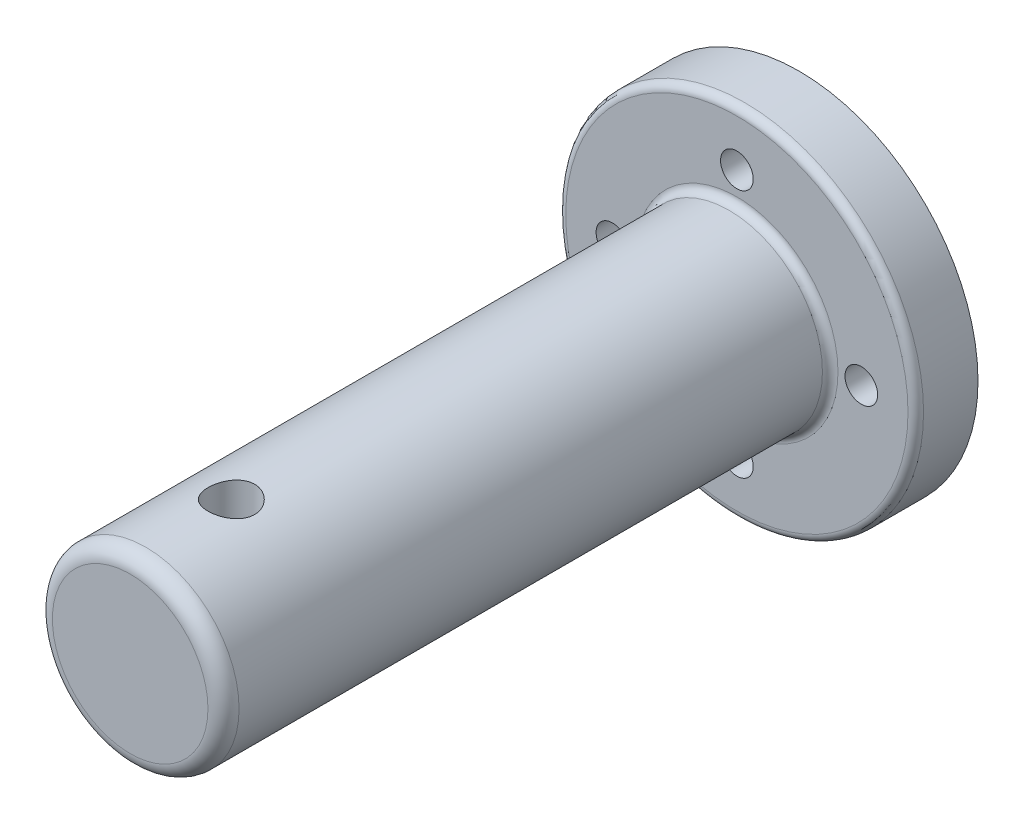
SolidWorks part; units mm, degrees
material "Alumina"
ref_plane "Front Plane" through (0, 0, 0) normal (0, 0, 1) x (1, 0, 0)
ref_plane "Top Plane" through (0, 0, 0) normal (0, 1, 0) x (1, 0, 0)
ref_plane "Right Plane" through (0, 0, 0) normal (1, 0, 0) x (0, 0, -1)
sketch "Sketch1" plane through (0, 0, 0) normal (0, 0, 1) x (1, 0, 0)
  circle A0 centre (0, 0) radius 11.5
  circle A1 centre (0, 0) radius 8 construction
  circle A2 centre (0, 8) radius 1.05
  circle A3 centre (0, 0) radius 11.5
  circle A4 centre (8, 0) radius 1.05
  circle A5 centre (0, 0) radius 11.5
  circle A6 centre (0, -8) radius 1.05
  circle A7 centre (0, 0) radius 11.5
  circle A8 centre (-8, 0) radius 1.05
  point P18 (0, 0)
  dimension "D1" = 23
  dimension "D2" = 16
  dimension "D3" = 2.1
  dimension "D4" = 4
extrude "Boss-Extrude1" add sketch "Sketch1" along normal blind 4 contours A0 A8 A6 A4 A2 region at (0, 0, 0)
sketch "Sketch2" plane through (0, 0, 4) normal (0, 0, 1) x (1, 0, 0)
  circle A0 centre (0, 0) radius 6
  dimension "D1" = 12
extrude "Boss-Extrude2" add sketch "Sketch2" along normal blind 39
sketch "Sketch3" plane through (0, 0, 0) normal (0, 0, -1) x (-1, 0, 0)
  circle A0 centre (0, 0) radius 4.25
  dimension "D1" = 8.5
extrude "Cut-Extrude1" cut sketch "Sketch3" against normal blind 9
fillet "Fillet1" radius 0.5 2 edges at (11.5, 0, 4) (6, 0, 4)
fillet "Fillet2" radius 1 1 edges at (6, 0, 43)
fillet "Fillet4" radius 1 1 edges at (-4.25, 0, 0)
fillet "Fillet5" radius 7 1 edges at (-4.25, 0, 9) second distance 2.5 first distance on face at (4.25, 0, 1)
sketch "Sketch5" plane through (0, 0, 0) normal (0, 1, 0) x (1, 0, 0)
  line L0 (-5, -43) -> (5, -43) construction
  circle A0 centre (0, -36.5) radius 1.5
  dimension "D1" = 3
  dimension "D2" = 6.5
extrude "Cut-Extrude2" cut sketch "Sketch5" against normal through all both and the other way through all
